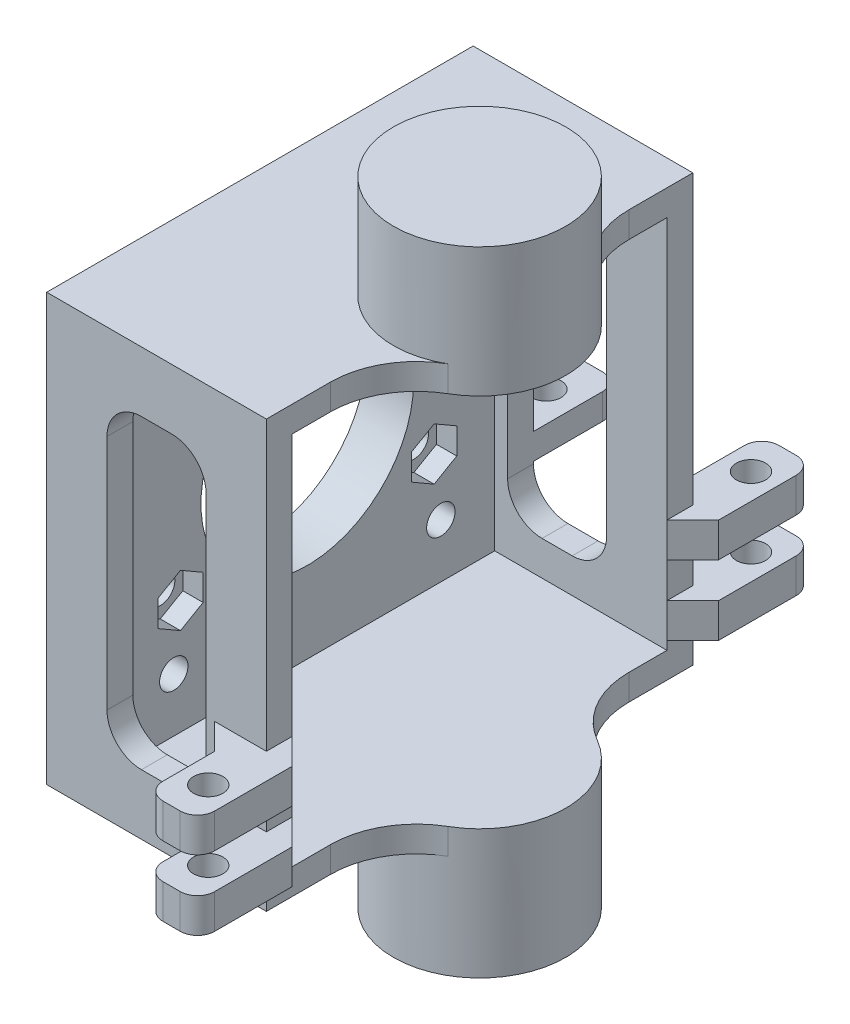
SolidWorks part; units mm, degrees
ref_plane "Alzado" through (0, 0, 0) normal (0, 0, 1) x (1, 0, 0)
ref_plane "Planta" through (0, 0, 0) normal (0, 1, 0) x (1, 0, 0)
ref_plane "Vista lateral" through (0, 0, 0) normal (1, 0, 0) x (0, 0, -1)
sketch "Croquis1" plane through (0, 0, 0) normal (1, 0, 0) x (0, 0, -1)
  line L0 (23.5, -23.5) -> (23.5, 23.5)
  line L1 (-15.5, -15.5) -> (15.5, -15.5) construction
  line L2 (-15.5, -15.5) -> (-15.5, 15.5) construction
  line L3 (-15.5, 15.5) -> (15.5, 15.5) construction
  line L4 (15.5, -15.5) -> (15.5, 15.5) construction
  line L5 (-15.5, -15.5) -> (15.5, 15.5) construction
  line L6 (-15.5, 15.5) -> (15.5, -15.5) construction
  line L7 (-23.5, 23.5) -> (23.5, 23.5)
  line L8 (-23.5, -23.5) -> (-23.5, 23.5)
  line L9 (-23.5, -23.5) -> (23.5, -23.5)
  circle A0 centre (-15.5, 15.5) radius 1.65
  circle A1 centre (15.5, 15.5) radius 1.65
  circle A2 centre (15.5, -15.5) radius 1.65
  circle A3 centre (-15.5, -15.5) radius 1.65
  point P0 (0, 0)
  point P16 (0, 0)
  dimension "D1" = 3.3
  dimension "D2" = 31
  dimension "D3" = 31
  dimension "D5" = 8
  dimension "D4" = 4
extrude "Saliente-Extruir1" add sketch "Croquis1" along normal blind 5.5
sketch "Croquis2" plane through (5.5, 0, 0) normal (1, 0, 0) x (0, 0, -1)
  line L1 (0, 13.9689) -> (2.625, 15.4845)
  line L2 (2.625, 15.4845) -> (2.625, 18.5155)
  line L3 (2.625, 18.5155) -> (0, 20.0311)
  line L4 (0, 20.0311) -> (-2.625, 18.5155)
  line L5 (-2.625, 18.5155) -> (-2.625, 15.4845)
  line L6 (-2.625, 15.4845) -> (0, 13.9689)
  line L24 (14.7224, -11.5311) -> (17.3474, -10.0155)
  line L25 (17.3474, -10.0155) -> (17.3474, -6.9845)
  line L26 (17.3474, -6.9845) -> (14.7224, -5.4689)
  line L27 (14.7224, -5.4689) -> (12.0974, -6.9845)
  line L28 (12.0974, -6.9845) -> (12.0974, -10.0155)
  line L29 (12.0974, -10.0155) -> (14.7224, -11.5311)
  line L30 (-17.3474, -6.9845) -> (-17.3474, -10.0155)
  line L31 (-17.3474, -10.0155) -> (-14.7224, -11.5311)
  line L32 (-14.7224, -11.5311) -> (-12.0974, -10.0155)
  line L33 (-12.0974, -10.0155) -> (-12.0974, -6.9845)
  line L34 (-12.0974, -6.9845) -> (-14.7224, -5.4689)
  line L35 (-14.7224, -5.4689) -> (-17.3474, -6.9845)
  circle A0 centre (0, 0) radius 17 construction
  circle A1 centre (0, 17) radius 2.625 construction
  point P26 (0, 0)
  dimension "D1" = 34
  dimension "D3" = 5.25
  dimension "D2" = 3
extrude "Cortar-Extruir1" cut sketch "Croquis2" against normal blind 2.35
sketch "Croquis7" plane through (5.5, 0, 0) normal (1, 0, 0) x (0, 0, -1)
  circle A0 centre (0, 0) radius 12.35
  dimension "D1" = 24.7
extrude "Cortar-Extruir2" cut sketch "Croquis7" against normal up to surface (5.5 mm away) up to face at (0, 0, 0)
sketch "Croquis8" plane through (5.5, 0, 0) normal (1, 0, 0) x (0, 0, -1)
  circle A0 centre (0, 17) radius 1.7
  circle A1 centre (14.7224, -8.5) radius 1.7
  circle A2 centre (-14.7224, -8.5) radius 1.7
  point P9 (0, 0)
  dimension "D1" = 3.4
  dimension "D2" = 3
extrude "Cortar-Extruir3" cut sketch "Croquis8" against normal up to surface (5.5 mm away) up to face at (0, 0, -12.35)
sketch "Croquis9" plane through (0, 0, 0) normal (1, 0, 0) x (0, 0, -1)
  line L0 (-24.75, -24.75) -> (24.75, -24.75)
  line L1 (-21.75, 21.75) -> (21.75, 21.75)
  line L2 (-21.75, 21.75) -> (-21.75, -21.75)
  line L3 (-21.75, -21.75) -> (21.75, -21.75)
  line L4 (21.75, 21.75) -> (21.75, -21.75)
  line L5 (-21.75, 21.75) -> (21.75, -21.75) construction
  line L6 (-21.75, -21.75) -> (21.75, 21.75) construction
  line L7 (24.75, 24.75) -> (24.75, -24.75)
  line L8 (-24.75, 24.75) -> (24.75, 24.75)
  line L9 (-24.75, 24.75) -> (-24.75, -24.75)
  point P0 (0, 0)
  dimension "D1" = 43.5
  dimension "D2" = 3
extrude "Saliente-Extruir2" add sketch "Croquis9" along normal blind 25.5
sketch "Croquis10" plane through (0, 21.75, 0) normal (0, 1, 0) x (1, 0, 0)
  line L0 (25.5, 24.75) -> (25.5, -24.75) construction
  circle A0 centre (25.5, 0) radius 10
  dimension "D1" = 20
extrude "Saliente-Extruir3" add sketch "Croquis10" along normal blind 15
mirror "Simetría1" about plane through (0, 0, 0) normal (0, 1, 0) of "Saliente-Extruir3"
sketch "Croquis11" plane through (0, 0, -24.75) normal (0, 0, -1) x (-1, 0, 0)
  line L12 (-7, -17.75) -> (-7, 17.75)
  line L13 (-7, 17.75) -> (-18.5, 17.75)
  line L14 (-18.5, 17.75) -> (-18.5, -17.75)
  line L15 (-18.5, -17.75) -> (-7, -17.75)
  line L16 (-7, -13.75) -> (-7, 13.75)
  line L17 (-11, 17.75) -> (-14.5, 17.75)
  line L18 (-18.5, 13.75) -> (-18.5, -13.75)
  line L19 (-14.5, -17.75) -> (-11, -17.75)
  arc A0 (-7, 13.75) -> (-11, 17.75) centre (-11, 13.75) ccw
  arc A1 (-14.5, 17.75) -> (-18.5, 13.75) centre (-14.5, 13.75) ccw
  arc A2 (-18.5, -13.75) -> (-14.5, -17.75) centre (-14.5, -13.75) ccw
  arc A3 (-7, -13.75) -> (-11, -17.75) centre (-11, -13.75) cw
  dimension "D2" = 4
  dimension "D1" = 7
extrude "Cortar-Extruir4" cut sketch "Croquis11" against normal up to surface (49.5 mm away) up to face at (12.75, 0, 24.75)
fillet "Redondeo1" radius 10 4 edges at (25.5, 23.25, 10) (25.5, 23.25, -10) (25.5, -23.25, -10) (25.5, -23.25, 10)
ref_plane "Plano1" through (0, -20.75, 0) normal (0, -1, 0) x (-1, 0, 0)
sketch "Croquis13" plane through (0, -20.75, 0) normal (0, -1, 0) x (1, 0, 0)
  line L0 (25.5, 0) -> (25.5, -35) construction
  line L1 (28.5, -24.75) -> (22.5, -24.75)
  line L2 (25.5, -24.75) -> (0, -24.75) construction
  line L3 (22.5, -24.75) -> (22.5, -35.75)
  line L4 (22.5, -35.75) -> (27.0226, -35.75)
  line L5 (28.5, -24.75) -> (28.5, -35.75)
  line L6 (28.5, -35.75) -> (23.9774, -35.75)
  circle A0 centre (25.5, 0) radius 10 construction
  circle A1 centre (25.5, 0) radius 10 construction
  circle A2 centre (25.5, 0) radius 35 construction
  circle A3 centre (25.5, 0) radius 31.5 construction
  circle A4 centre (25.5, -31.5) radius 1.7
  point P16 (25.5, -24.75)
  point P18 (25.5, -24.75)
  dimension "D1" = 70
  dimension "D3" = 3.4
  dimension "D4" = 6
  dimension "D5" = 11
  dimension "D2" = 3.5
extrude "Saliente-Extruir5" add sketch "Croquis13" against normal blind 12.1
sketch "Croquis14" plane through (0, 0, -24.75) normal (0, 0, -1) x (-1, 0, 0)
  line L0 (-28.5, -14.7) -> (-22.5, -14.7) construction
  line L1 (-28.5, -8.65) -> (-28.5, -20.75) construction
  line L2 (-22.5, -8.65) -> (-22.5, -20.75) construction
  line L3 (-28.5, -16.75) -> (-22.5, -16.75)
  line L5 (-28.5, -12.65) -> (-28.5, -16.75)
  line L6 (-22.5, -12.65) -> (-22.5, -16.75)
  line L7 (-28.5, -12.65) -> (-22.5, -12.65)
  dimension "D1" = 4.1
extrude "Cortar-Extruir5" cut sketch "Croquis14" along normal up to surface (11 mm away) up to face at (25.5, -14.7, -35.75)
mirror "Simetría2" about plane through (0, 0, 0) normal (0, 0, 1) of "Cortar-Extruir5", "Saliente-Extruir5"
chamfer "Chaflán1" distance 3 angle 45 8 edges at (25.5, -18.75, -24.75) (22.5, -10.65, -24.75) (22.5, -18.75, -24.75) (25.5, -10.65, -24.75) (25.5, -10.65, 24.75) (22.5, -10.65, 24.75) (22.5, -18.75, 24.75) (25.5, -18.75, 24.75)
sketch "Croquis15" plane through (0, 0, -24.75) normal (0, 0, -1) x (-1, 0, 0)
  line L0 (0, 0) -> (-14.3445, 0) construction
  line L1 (0, -24.75) -> (0, 24.75) construction
  line L2 (0, 13.5) -> (-7, 13.5)
  line L3 (0, 13.5) -> (0, 10.5)
  line L4 (0, 10.5) -> (-7, 10.5)
  line L5 (-7, 13.5) -> (-7, 10.5)
  line L6 (-7, -13.75) -> (-7, 13.75) construction
  line L7 (0, -10.5) -> (-7, -10.5)
  line L8 (-7, -13.5) -> (-7, -10.5)
  line L9 (0, -13.5) -> (-7, -13.5)
  line L10 (0, -13.5) -> (0, -10.5)
  dimension "D1" = 3
  dimension "D2" = 21
extrude "Saliente-Extruir6" add sketch "Croquis15" along normal blind 10
sketch "Croquis16" plane through (0, -13.5, 0) normal (0, -1, 0) x (1, 0, 0)
  line L0 (3.5, -24.75) -> (3.5, -34.75) construction
  line L1 (7, -24.75) -> (0, -24.75) construction
  line L2 (7, -34.75) -> (0, -34.75) construction
  line L3 (0, -29.75) -> (7, -29.75) construction
  line L4 (0, -34.75) -> (0, -24.75) construction
  line L5 (7, -34.75) -> (7, -24.75) construction
  circle A0 centre (3.5, -29.75) radius 1.7
  dimension "D1" = 3.4
extrude "Cortar-Extruir6" cut sketch "Croquis16" against normal up to surface (27 mm away) contours A0 up to face at (3.5, 13.5, -29.75)
fillet "Redondeo2" radius 2 4 edges at (0, -12, -34.75) (7, -12, -34.75) (7, 12, -34.75) (0, 12, -34.75)
fillet "Redondeo4" radius 2 6 edges at (28.5, -18.75, -35.75) (28.5, -18.75, 35.75) (22.5, -18.75, 35.75) (22.5, -18.75, -35.75) (22.5, -10.65, -35.75) (28.5, -10.65, -35.75)
sketch "Croquis18" plane through (0, 0, 0) normal (-1, 0, 0) x (0, 0, 1)
  circle A0 centre (-15.5, 15.5) radius 3.25
  circle A1 centre (15.5, 15.5) radius 3.25
  circle A2 centre (15.5, -15.5) radius 3.25
  circle A3 centre (-15.5, -15.5) radius 3.25
  point P12 (0, 0)
  dimension "D1" = 6.5
  dimension "D2" = 4
extrude "Cortar-Extruir7" cut sketch "Croquis18" against normal blind 2.5
